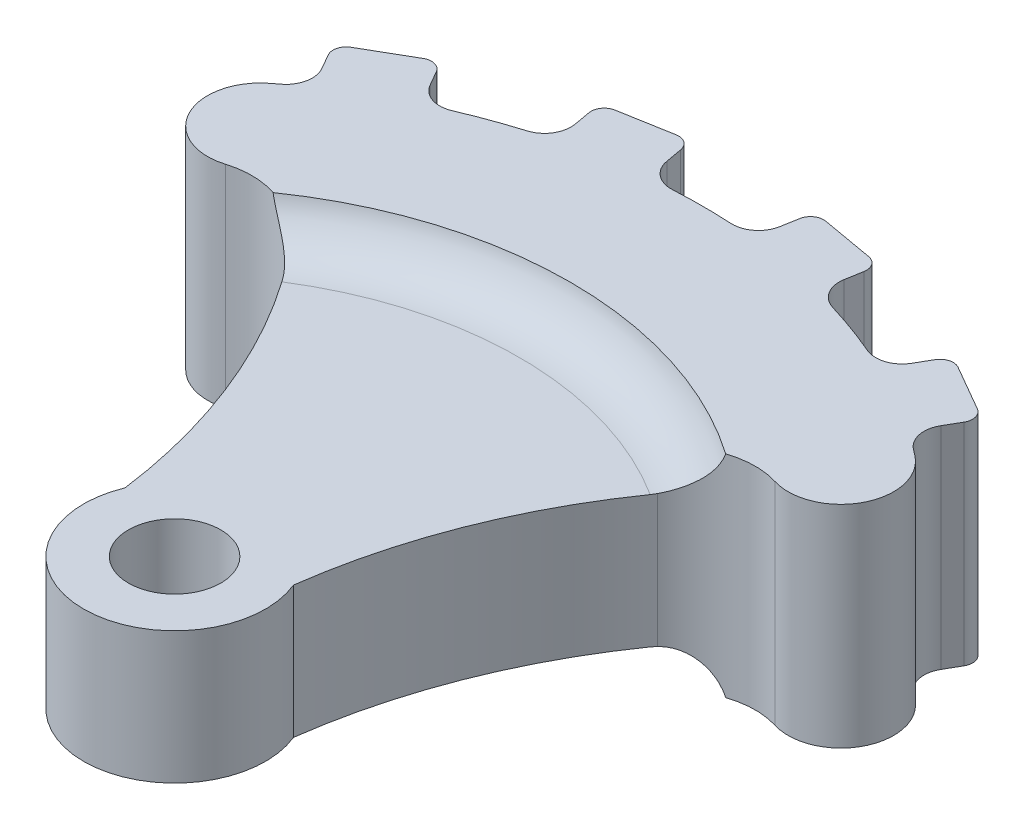
SolidWorks part; units mm, degrees
ref_plane "Front Plane" through (0, 0, 0) normal (0, 0, 1) x (1, 0, 0)
ref_plane "Top Plane" through (0, 0, 0) normal (0, 1, 0) x (1, 0, 0)
ref_plane "Right Plane" through (0, 0, 0) normal (1, 0, 0) x (0, 0, -1)
sketch "Sketch1" plane through (0, 0, 0) normal (0, 1, 0) x (1, 0, 0)
  line L0 (-9.701, 19.8026) -> (-8.6728, 18.0217)
  line L1 (-12.299, 18.3026) -> (-9.701, 19.8026)
  line L2 (-12.299, 18.3026) -> (-11.2709, 16.5217)
  line L3 (-5.2975, 21.4053) -> (-4.9404, 19.3802)
  line L4 (-5.2975, 21.4053) -> (-2.343, 21.9262)
  line L5 (-2.343, 21.9262) -> (-1.986, 19.9012)
  line L6 (-11, 19.0526) -> (0, 0) construction
  line L7 (-3.8203, 21.6658) -> (0, 0) construction
  line L8 (0, -246.4085) -> (0, 12074.0173) construction
  line L9 (12.299, 18.3026) -> (11.2709, 16.5217)
  line L10 (12.299, 18.3026) -> (9.701, 19.8026)
  line L11 (9.701, 19.8026) -> (8.6728, 18.0217)
  line L12 (5.2975, 21.4053) -> (4.9404, 19.3802)
  line L13 (5.2975, 21.4053) -> (2.343, 21.9262)
  line L14 (2.343, 21.9262) -> (1.986, 19.9012)
  arc A1 (8.5754, 12.307) -> (-8.5754, 12.307) centre (0, 0) ccw
  arc A2 (12.2222, 15.8309) -> (-12.2222, 15.8309) centre (0, 0) ccw
  arc A3 (7.0978, 11.2097) -> (3.1906, 1.3124) centre (25, -1.5775) ccw
  arc A4 (-7.0978, 11.2097) -> (-3.1906, 1.3124) centre (-25, -1.5775) cw
  arc A5 (12.2222, 15.8309) -> (10.4156, 12.3351) centre (11, 14.2478) cw
  arc A6 (10.4156, 12.3351) -> (7.0978, 11.2097) centre (9.539, 9.466) ccw
  arc A7 (-10.4156, 12.3351) -> (-7.0978, 11.2097) centre (-9.539, 9.466) cw
  arc A8 (-12.2222, 15.8309) -> (-10.4156, 12.3351) centre (-11, 14.2478) ccw
  arc A9 (-3.1906, 1.3124) -> (3.1906, 1.3124) centre (0, 0) ccw
  point P22 (0, 0)
  dimension "D6" = 20
  dimension "D7" = 15
  dimension "D8" = 22
  dimension "D9" = 2
  dimension "D10" = 3.45
  dimension "D11" = 3
  dimension "D12" = 22
  dimension "D13" = 50
  dimension "D1" = 3
  dimension "D2" = 10
  dimension "D4" = 20
  dimension "D5" = 22
  dimension "D3" = 2
extrude "Boss-Extrude1" add sketch "Sketch1" along normal mid plane 5 contours A4 A9 A3 A6 A1 A7 region at (0, 0, -7.364)
extrude "Boss-Extrude2" add sketch "Sketch1<3>" along normal mid plane 8 contours A2 A8 A7 A1 A6 A5 | A2 L12 L13 L14 | A2 L5 L4 L3 | A2 L0 L1 L2 | A2 L9 L10 L11 region at (-10.4953, 0, -18.1783) region at (0, 0, -16.1314) region at (-3.645, 0, -20.6717) region at (3.645, 0, -20.6717) region at (10.4953, 0, -18.1783)
sketch "Sketch1<3>" plane through (0, 0, 0) normal (0, 1, 0) x (1, 0, 0) same geometry as "Sketch1"
fillet "Fillet1" radius 1 8 edges at (-11.2709, 0, -16.5217) (11.2709, 0, -16.5217) (8.6728, 0, -18.0217) (4.9404, 0, -19.3802) (-1.986, 0, -19.9012) (1.986, 0, -19.9012) (-4.9404, 0, -19.3802) (-8.6728, 0, -18.0217)
fillet "Fillet2" radius 0.5 8 edges at (12.299, 0, -18.3026) (9.701, 0, -19.8026) (5.2975, 0, -21.4053) (2.343, 0, -21.9262) (-2.343, 0, -21.9262) (-5.2975, 0, -21.4053) (-9.701, 0, -19.8026) (-12.299, 0, -18.3026)
sketch "Sketch2" plane through (0, 2.5, 0) normal (0, 1, 0) x (1, 0, 0)
  circle A0 centre (0, 0) radius 1.75
  dimension "D1" = 3.5
extrude "Cut-Extrude1" cut sketch "Sketch2" against normal blind 8
fillet "Fillet3" radius 2 2 edges at (0, -2.5, -15) (0, 2.5, -15)
